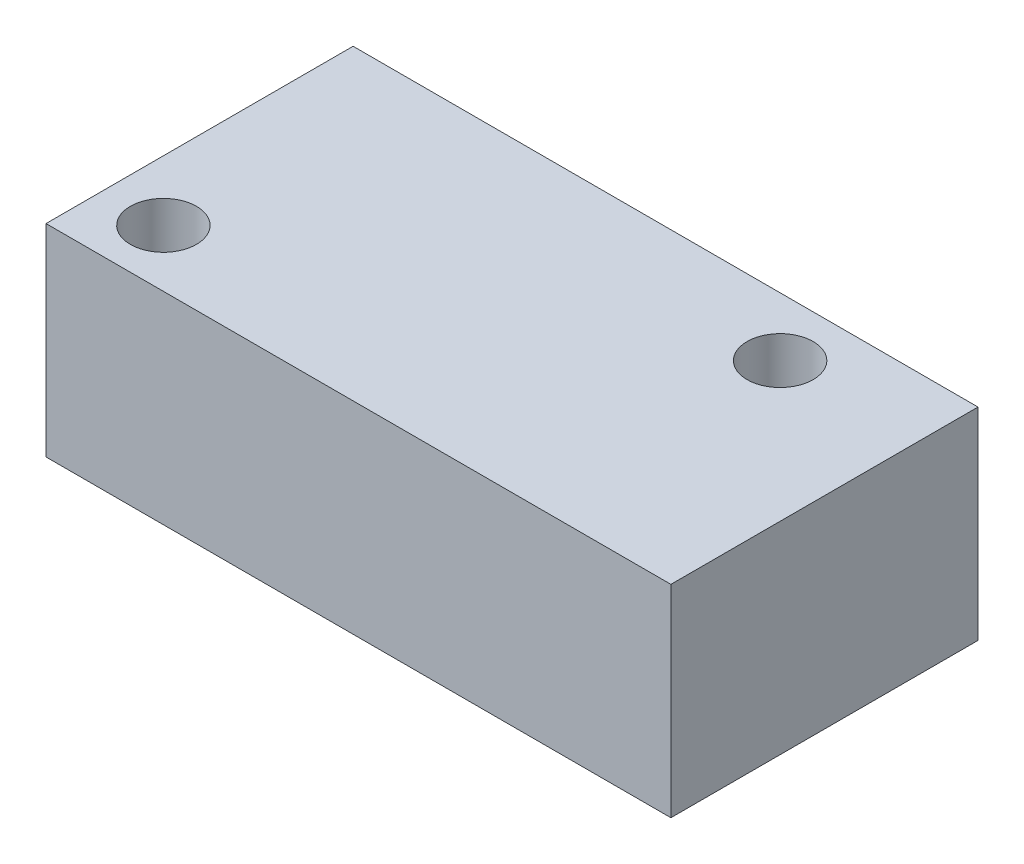
SolidWorks part; units mm, degrees
ref_plane "Front Plane" through (0, 0, 0) normal (0, 0, 1) x (1, 0, 0)
ref_plane "Top Plane" through (0, 0, 0) normal (0, 1, 0) x (1, 0, 0)
ref_plane "Right Plane" through (0, 0, 0) normal (1, 0, 0) x (0, 0, -1)
sketch "Sketch2" plane through (0, 0, 0) normal (0, 1, 0) x (1, 0, 0)
  line L1 (0, 0) -> (32.15, 0)
  line L2 (0, 0) -> (0, 15.8)
  line L3 (0, 15.8) -> (32.15, 15.8)
  line L4 (32.15, 0) -> (32.15, 15.8)
  dimension "D1" = 32.15
  dimension "D2" = 15.8
extrude "Boss-Extrude1" add sketch "Sketch2" along normal blind 10.4
sketch "Sketch3" plane through (0, 10.4, 0) normal (0, 1, 0) x (1, 0, 0)
  line L0 (0, 0) -> (32.15, 0) construction
  line L1 (0, 15.8) -> (0, 0) construction
  line L2 (32.15, 0) -> (32.15, 15.8) construction
  line L3 (32.15, 15.8) -> (0, 15.8) construction
  circle A0 centre (3.1, 2.94) radius 1.7
  circle A1 centre (24.99, 12.78) radius 1.7
  point P8 (0, 0)
  point P11 (0, 0)
  point P12 (32.15, 13.7278)
  dimension "D1" = 3.4
  dimension "D2" = 3.4
  dimension "D5" = 7.16
  dimension "D3" = 2.94
  dimension "D4" = 3.1
  dimension "D6" = 3.02
extrude "Cut-Extrude1" cut sketch "Sketch3" against normal blind 10.4
sketch "Sketch4" plane through (0, 0, -15.8) normal (0, 0, -1) x (-1, 0, 0)
  line L0 (-32.15, 0) -> (0, 0) construction
  line L1 (0, 10.4) -> (0, 0) construction
  circle A0 centre (-4.95, 5.2) radius 4.6
  point P2 (-5.3361, 4.6613)
  point P3 (-5.1994, 5.0312)
  dimension "D1" = 9.2
  dimension "D2" = 5.2
  dimension "D3" = 4.95
extrude "Boss-Extrude2" [suppressed] add sketch "Sketch4" along normal blind 2
sketch "Sketch5" [suppressed] plane through (0, 0, -17.8) normal (0, 0, -1) x (-1, 0, 0)
  circle A0 centre (-4.95, 5.2) radius 1.25
extrude "Boss-Extrude3" [suppressed] add sketch "Sketch5" along normal blind 1.1
ref_axis "Axis1" [suppressed] through (4.95, 5.2, -22.5074) along (0, 0, 1)
ref_plane "Plane3" through (0, 5.2, 0) normal (0, 1, 0) x (1, 0, 0)
sketch "Sketch13" plane through (0, 5.2, 0) normal (0, 1, 0) x (1, 0, 0)
  line L0 (4.8702, 15.8) -> (9.4702, 15.8)
  line L2 (4.8702, 15.8) -> (4.8702, 19)
  line L3 (32.15, 15.8) -> (0, 15.8) construction
  line L4 (7.1299, 17.2477) -> (7.1299, 17.8477)
  arc A3 (4.8702, 19) -> (7.1299, 17.8477) centre (4.8702, 16.2082) cw
  arc A4 (7.1299, 17.2477) -> (9.4702, 15.8) centre (6.997, 14.4174) cw
  point P3 (0, 0)
  point P6 (6.711, 17.8)
  point P7 (0, 0)
  dimension "D2" = 4.6
  dimension "D1" = 0.6
  dimension "D5" = 2.7918
  dimension "D3" = 3.2
revolve "Revolve1" add sketch "Sketch13" angle 360 about L2
